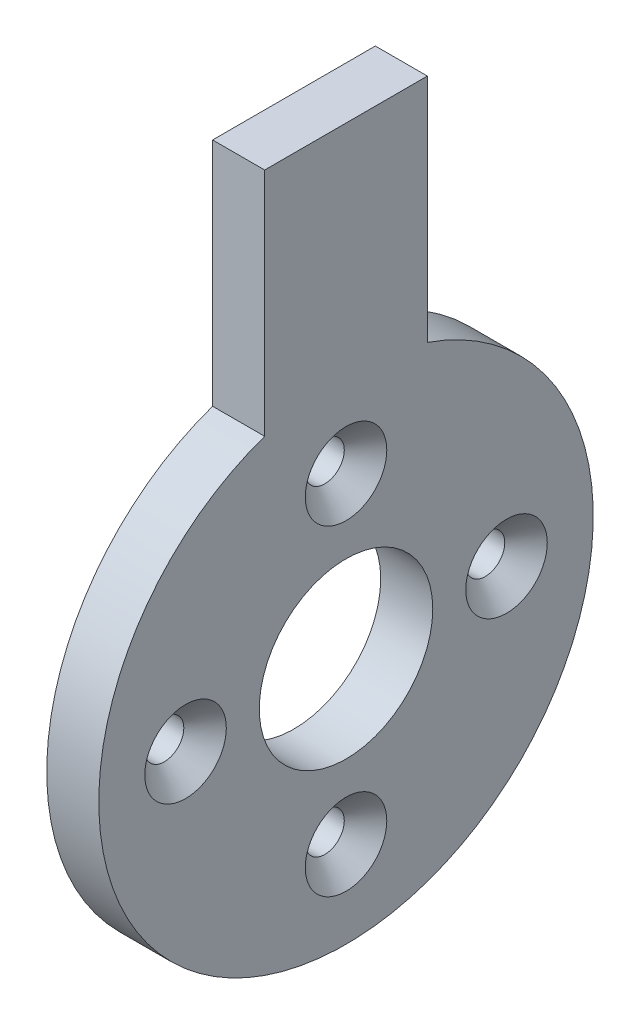
SolidWorks part; units mm, degrees
ref_plane "Front Plane" through (0, 0, 0) normal (0, 0, 1) x (1, 0, 0)
ref_plane "Top Plane" through (0, 0, 0) normal (0, 1, 0) x (1, 0, 0)
ref_plane "Right Plane" through (0, 0, 0) normal (1, 0, 0) x (0, 0, -1)
sketch "Sketch1" plane through (0, 0, 0) normal (1, 0, 0) x (0, 0, -1)
  circle A1 centre (0, 0) radius 28.5
  dimension "D2" = 57
extrude "Boss-Extrude1" add sketch "Sketch1" along normal mid plane 6
sketch "Sketch2" plane through (3, 0, 0) normal (1, 0, 0) x (0, 0, -1)
  circle A0 centre (0, 0) radius 10
  dimension "D1" = 20
extrude "Cut-Extrude1" cut sketch "Sketch2" against normal through all
sketch "Sketch3" plane through (0, 0, 0) normal (1, 0, 0) x (0, 0, -1)
  line L0 (-9.3792, 53.5) -> (-9.3792, 26.9125)
  line L1 (-9.3792, 53.5) -> (9.3792, 53.5)
  line L5 (9.3792, 53.5) -> (9.3792, 26.9125)
  circle A3 centre (0, 0) radius 28.5 construction
  arc A4 (9.3792, 26.9125) -> (-9.3792, 26.9125) centre (0, 0) ccw
  point P0 (0, 30.4396)
  dimension "D1" = 25
extrude "Boss-Extrude2" add sketch "Sketch3" along normal mid plane 6
sketch "Sketch4" plane through (3, 0, 0) normal (1, 0, 0) x (0, 0, -1)
  circle A0 centre (18.5, 0) radius 2
  arc A1 (-9.3792, 26.9125) -> (9.3792, 26.9125) centre (0, 0) ccw construction
  arc A2 (-9.3792, 26.9125) -> (9.3792, 26.9125) centre (0, 0) ccw
  circle A3 centre (0, -18.5) radius 2
  circle A5 centre (0, 18.5) radius 2
  circle A6 centre (-18.5, 0) radius 2
  point P15 (0, 0)
  dimension "D1" = 4
hole_wizard "CSK for M4 Flat Head Machine Screw1" positions "3DSketch1" profile "Sketch5" countersink size "M4" standard "ANSI Metric" end condition through all
sketch3d "3DSketch1"
  point P0 (3, 18.5, 0)
  point P3 (3, 0, -18.5)
  point P6 (3, -18.5, 0)
  point P9 (3, 0, 18.5)
sketch "Sketch5" plane through (3, 18.5, 0) normal (0, 1, 0) x (0, 0, -1)
  line L0 (0, 0) -> (0, 6)
  line L1 (0, 6) -> (2.25, 6)
  line L2 (2.25, 6) -> (2.25, 2.45)
  line L3 (2.25, 2.45) -> (4.7, 0)
  line L5 (4.7, 0) -> (0, 0)
  line L6 (-2.25, 2.45) -> (-4.7, 0) construction
  line L11 (0, -6.35) -> (0, 107.95) construction
  dimension "Thru Hole Dia." = 4.5
  dimension "Thru Hole Depth" = 6
  dimension "Near C'Sink Dia." = 9.4
  dimension "Near C'Sink Angle" = 90
